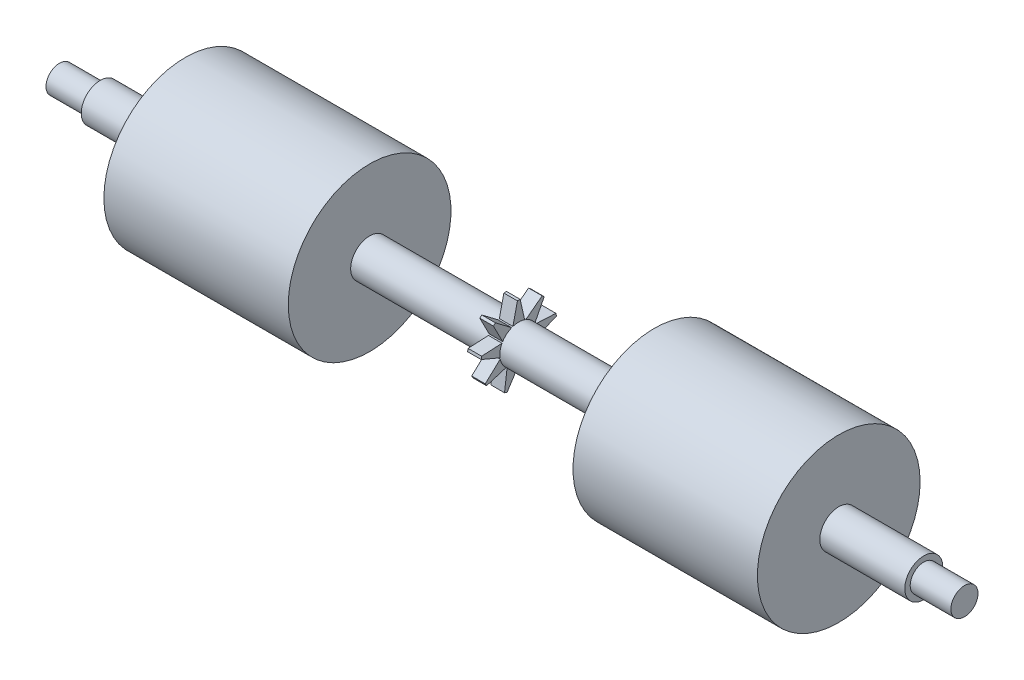
SolidWorks part; units mm, degrees
ref_plane "Plan de face" through (0, 0, 0) normal (0, 0, 1) x (1, 0, 0)
ref_plane "Plan de dessus" through (0, 0, 0) normal (0, 1, 0) x (1, 0, 0)
ref_plane "Plan de droite" through (0, 0, 0) normal (1, 0, 0) x (0, 0, -1)
sketch "Esquisse1" plane through (0, 0, 0) normal (1, 0, 0) x (0, 0, -1)
  circle A0 centre (0, 0) radius 7
extrude "Boss.-Extru.2" add sketch "Esquisse1" along normal blind 151.845 and the other way blind 151.845
sketch "Esquisse3" plane through (0, 0, 0) normal (0, 0, 1) x (1, 0, 0)
  line L0 (-120.5, 0) -> (-52.5, 0)
  line L1 (120.5, 0) -> (120.5, 35)
  line L2 (120.5, 35) -> (52.5, 35)
  line L3 (52.5, 35) -> (52.5, 0)
  line L4 (52.5, 0) -> (120.5, 0)
  line L5 (-120.5, 0) -> (-120.5, 30)
  line L7 (-52.5, 30) -> (-52.5, 0)
  line L10 (-120.5, 30) -> (-52.5, 30)
  point P14 (-86.5, 30)
  dimension "D1" = 120.5
  dimension "D2" = 120.5
revolve "Révolution2" add sketch "Esquisse3" angle 360 about L0
sketch "Esquisse4" plane through (-151.845, 0, 0) normal (-1, 0, 0) x (0, 0, 1)
  circle A0 centre (0, 0) radius 5
extrude "Boss.-Extru.3" add sketch "Esquisse4" along normal blind 15
sketch "Esquisse5" plane through (151.845, 0, 0) normal (1, 0, 0) x (0, 0, -1)
  circle A0 centre (0, 0) radius 5
extrude "Boss.-Extru.4" add sketch "Esquisse5" along normal blind 15
sketch "Esquisse6" plane through (0, 0, 0) normal (1, 0, 0) x (0, 0, -1)
  line L0 (-0.4954, 14) -> (-2.17, 6.6552)
  line L1 (-2.6108, 6.4951) -> (-2.17, 6.6552)
  line L2 (-0.4954, 14) -> (0.5, 14)
  line L3 (0.5, 14) -> (2.175, 6.6535)
  line L4 (8.6196, 11.0429) -> (2.6156, 6.4928)
  line L5 (9.382, 10.4031) -> (5.9429, 3.6987)
  line L6 (8.6196, 11.0429) -> (9.382, 10.4031)
  line L7 (13.7012, 2.9186) -> (6.1771, 3.2924)
  line L8 (13.874, 1.9384) -> (6.93, -0.9868)
  line L9 (13.7012, 2.9186) -> (13.874, 1.9384)
  line L10 (12.3718, -6.5713) -> (6.8482, -1.4487)
  line L11 (11.8741, -7.4333) -> (4.6744, -5.2107)
  line L12 (12.3718, -6.5713) -> (11.8741, -7.4333)
  line L13 (5.2534, -12.9865) -> (4.3149, -5.5119)
  line L14 (4.318, -13.3269) -> (0.2314, -6.9964)
  line L15 (5.2534, -12.9865) -> (4.318, -13.3269)
  line L16 (-4.3233, -13.3252) -> (-0.2376, -6.996)
  line L17 (-5.2586, -12.9848) -> (-4.3199, -5.5085)
  line L18 (-4.3233, -13.3252) -> (-5.2586, -12.9848)
  line L19 (-11.8771, -7.4289) -> (-4.679, -5.2067)
  line L20 (-12.3748, -6.5669) -> (-6.85, -1.4431)
  line L21 (-11.8771, -7.4289) -> (-12.3748, -6.5669)
  line L22 (-13.8736, 1.9434) -> (-6.9311, -0.9812)
  line L23 (-13.7007, 2.9236) -> (-6.175, 3.2975)
  line L24 (-13.8736, 1.9434) -> (-13.7007, 2.9236)
  line L25 (-9.3786, 10.4063) -> (-5.9402, 3.7035)
  line L26 (-8.6161, 11.0461) -> (-2.6108, 6.4951)
  line L27 (-9.3786, 10.4063) -> (-8.6161, 11.0461)
  line L28 (-5.9402, 3.7035) -> (-6.175, 3.2975)
  line L29 (-6.9311, -0.9812) -> (-6.85, -1.4431)
  line L30 (-4.679, -5.2067) -> (-4.3199, -5.5085)
  line L31 (-0.2376, -6.996) -> (0.2314, -6.9964)
  line L32 (4.6744, -5.2107) -> (4.3149, -5.5119)
  line L33 (6.93, -0.9868) -> (6.8482, -1.4487)
  line L34 (5.9429, 3.6987) -> (6.1771, 3.2924)
  line L35 (2.175, 6.6535) -> (2.6156, 6.4928)
  circle A1 centre (0, 0) radius 7 construction
  point P11 (0.0023, 14)
  point P48 (-0.0002, -0.0001)
  dimension "D1" = 9
extrude "Boss.-Extru.6" add sketch "Esquisse6" along normal blind 2.5 and the other way blind 2.5
sketch "Esquisse11" plane through (120.5, 0, 0) normal (1, 0, 0) x (0, 0, -1)
  circle A0 centre (0, 0) radius 30
  circle A1 centre (0, 0) radius 35
extrude "Enlèv. mat.-Extru.1" cut sketch "Esquisse11" against normal up to surface (68 mm away) up to face at (52.5, 0, -7)
